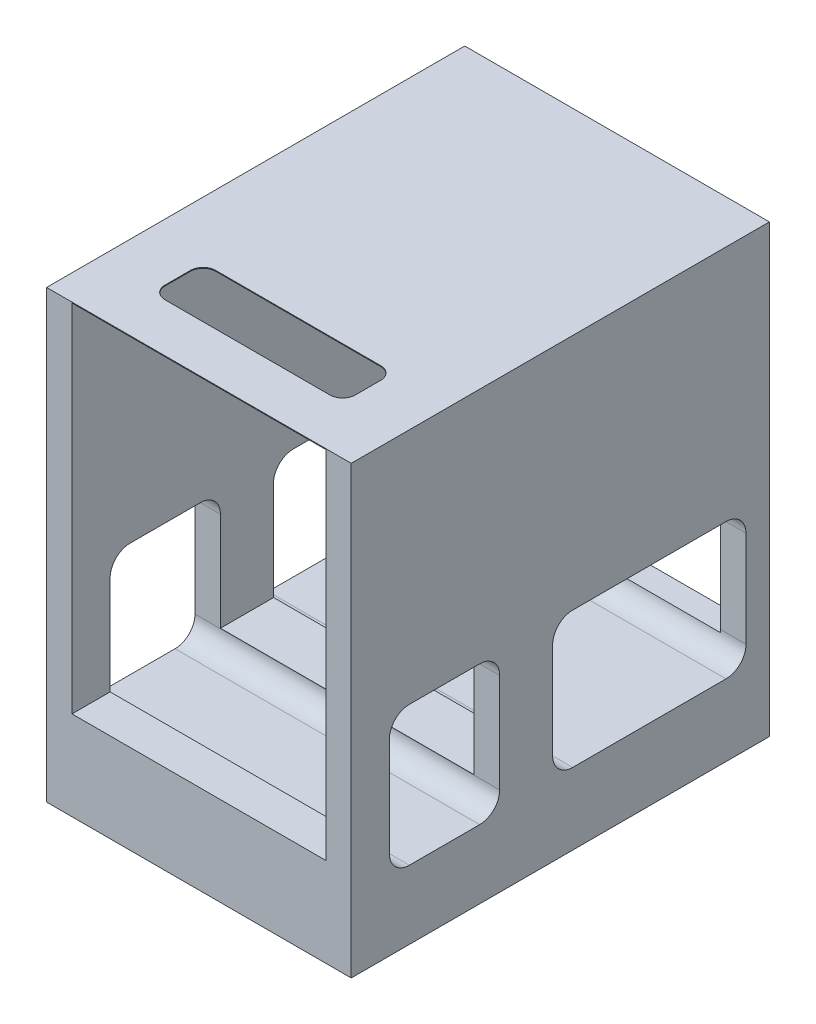
SolidWorks part; units mm, degrees
ref_plane "Front Plane" through (0, 0, 0) normal (0, 0, 1) x (1, 0, 0)
ref_plane "Top Plane" through (0, 0, 0) normal (0, 1, 0) x (1, 0, 0)
ref_plane "Right Plane" through (0, 0, 0) normal (1, 0, 0) x (0, 0, -1)
sketch "Sketch1" plane through (0, 0, 0) normal (0, 1, 0) x (1, 0, 0)
  line L0 (0, 107.4332) -> (0, -101.5151) construction
  line L1 (76.1125, -101.5151) -> (-76.1125, -101.5151)
  line L2 (76.1125, -101.5151) -> (76.1125, 107.4332)
  line L3 (76.1125, 107.4332) -> (-76.1125, 107.4332)
  line L4 (-76.1125, -101.5151) -> (-76.1125, 107.4332)
  line L5 (-76.1125, -597.4296) -> (-76.1125, 267.5849) construction
extrude "Boss-Extrude1" add sketch "Sketch1" along normal up to surface (222.72 mm away)
sketch "Sketch5" plane through (0, 0, 101.5151) normal (0, 0, 1) x (1, 0, 0)
  line L4 (76.1125, 222.72) -> (-76.1125, 222.72)
  line L5 (-76.1125, 222.72) -> (-76.1125, 0)
  line L6 (-76.1125, 0) -> (76.1125, 0)
  line L7 (76.1125, 0) -> (76.1125, 222.72)
  line L8 (65.8631, 222.72) -> (-65.8631, 222.72)
  line L9 (-65.8631, 222.72) -> (-65.8631, 0)
  line L10 (-65.8631, 0) -> (65.8631, 0)
  line L11 (65.8631, 0) -> (65.8631, 222.72)
  point P8 (0, 222.72)
  dimension "D1" = 0
extrude "Boss-Extrude2" [suppressed] add sketch "Sketch5" against normal up to vertex up to point (-76.1125, 0, -107.4332)
sketch "Sketch2" plane through (0, 0, 0) normal (1, 0, 0) x (0, 0, -1)
  line L1 (158.6159, 359.32) -> (-12.7, 359.32)
  line L2 (158.6159, 359.32) -> (158.6159, 232.32)
  line L3 (158.6159, 232.32) -> (-12.7, 232.32)
  line L4 (-12.7, 359.32) -> (-12.7, 232.32)
  line L5 (-108.9263, 232.32) -> (-218.9263, 232.32) construction
  dimension "D2" = 12.7
  dimension "D3" = 171.3159
  dimension "D4" = 127
extrude "Cut-Extrude1" cut sketch "Sketch2" against normal through all both and the other way through all rebuild error yes
sketch "Sketch6" plane through (-76.1125, 0, 0) normal (-1, 0, 0) x (0, 0, 1)
  line L0 (-107.4332, 6.35) -> (12.7, 6.35)
  line L8 (-107.4332, 222.72) -> (-107.4332, 0)
  line L9 (-107.4332, 0) -> (101.5151, 0)
  line L10 (101.5151, 0) -> (101.5151, 222.72)
  line L11 (101.5151, 222.72) -> (-107.4332, 222.72)
  line L14 (-107.4332, 6.35) -> (-107.4332, 0)
  line L15 (-107.4332, 0) -> (101.5151, 0)
  line L16 (101.5151, 0) -> (101.5151, 222.72)
  line L17 (101.5151, 222.72) -> (-107.4332, 222.72)
  dimension "D2" = 6.35
  dimension "D1" = 0
extrude "Boss-Extrude3" add sketch "Sketch6" along normal blind 50.8 rebuild error yes
mirror "Mirror1" about plane through (0, 0, 0) normal (1, 0, 0) rebuild error yes
sketch "Sketch7" plane through (0, 0, -107.4332) normal (0, 0, -1) x (-1, 0, 0)
  line L0 (76.1125, 222.32) -> (-76.1125, 222.32) construction
  line L3 (69.7625, 44.52) -> (-69.7625, 44.52)
  line L6 (69.7625, 0) -> (69.7625, 215.97)
  line L7 (-69.7625, 215.97) -> (-69.7625, 0)
  line L8 (69.7625, 215.97) -> (-69.7625, 215.97)
  line L9 (69.7625, 44.52) -> (69.7625, 222.32)
  line L10 (-69.7625, 222.32) -> (-69.7625, 44.52)
  line L11 (69.7625, 222.32) -> (-69.7625, 222.32)
  dimension "D3" = 177.8
  dimension "D1" = 6.35
extrude "Cut-Extrude4" cut sketch "Sketch7" against normal through all
sketch "Sketch9" plane through (0, 0, 12.7) normal (0, 0, -1) x (-1, 0, 0)
  line L0 (-76.1125, 168.275) -> (-126.9125, 168.275)
  line L7 (76.1125, 222.72) -> (-76.1125, 222.72)
  line L8 (76.1125, 222.72) -> (-76.1125, 222.72)
  line L12 (-76.1125, 222.32) -> (-69.7625, 222.32)
  line L14 (-69.7625, 222.32) -> (69.7625, 222.32)
  line L16 (69.7625, 222.32) -> (76.1125, 222.32)
  line L17 (76.1125, 222.32) -> (76.1125, 222.72)
  line L23 (-76.1125, 222.72) -> (-76.1125, 222.32)
  line L29 (76.1125, 222.72) -> (76.1125, 222.72)
  line L35 (-76.1125, 222.72) -> (-76.1125, 168.275)
  dimension "D1" = 0
extrude "Cut-Extrude6" cut sketch "Sketch9" against normal through all rebuild error yes
sketch "Sketch10" plane through (-69.7625, 0, 0) normal (1, 0, 0) x (0, 0, -1)
  line L6 (107.4332, 44.52) -> (107.4332, 222.32)
  line L9 (107.4332, 222.32) -> (-101.5151, 222.32)
  line L10 (-101.5151, 222.32) -> (-101.5151, 44.52)
  line L11 (-101.5151, 44.52) -> (107.4332, 44.52)
  line L18 (107.4332, 44.52) -> (107.4332, 222.32)
  line L21 (107.4332, 222.32) -> (-101.5151, 222.32)
  line L22 (-101.5151, 222.32) -> (-101.5151, 44.52)
  line L24 (-101.5151, 44.52) -> (107.4332, 44.52)
  dimension "D1" = 0
extrude "Boss-Extrude4" add sketch "Sketch10" along normal blind 6.35
mirror "Mirror2" about plane through (0, 0, 0) normal (1, 0, 0) of "Boss-Extrude4"
chamfer "Chamfer1" distance 19.05 angle 45 rebuild error yes
sketch "Sketch12" plane through (0, 222.32, 0) normal (0, -1, 0) x (1, 0, 0)
  line L0 (63.4125, -107.4332) -> (76.1125, -107.4332) construction
  line L4 (-63.4125, -107.4332) -> (63.4125, -107.4332)
  line L5 (63.4125, -107.4332) -> (63.4125, 101.5151)
  line L6 (63.4125, 101.5151) -> (-63.4125, 101.5151)
  line L7 (-63.4125, 101.5151) -> (-63.4125, -107.4332)
  line L8 (-63.4125, -107.4332) -> (63.4125, -107.4332)
  line L9 (63.4125, -107.4332) -> (63.4125, 101.5151)
  line L10 (63.4125, 101.5151) -> (-63.4125, 101.5151)
  line L11 (-63.4125, 101.5151) -> (-63.4125, -107.4332)
  line L13 (-63.4125, -107.4332) -> (63.4125, -107.4332)
  dimension "D1" = 0
extrude "Boss-Extrude5" add sketch "Sketch12" along normal blind 12.7 rebuild error yes
sketch "Sketch13" plane through (0, 222.72, 0) normal (0, 1, 0) x (1, 0, 0)
  line L0 (0, -51.8774) -> (0, -77.2774) construction
  line L1 (41.2049, -51.8774) -> (-41.2049, -51.8774)
  line L2 (47.5549, -58.2274) -> (47.5549, -70.9274)
  line L3 (41.2049, -77.2774) -> (-41.2049, -77.2774)
  line L4 (-47.5549, -58.2274) -> (-47.5549, -70.9274)
  arc A0 (-41.2049, -51.8774) -> (-47.5549, -58.2274) centre (-41.2049, -58.2274) ccw
  arc A1 (-41.2049, -77.2774) -> (-47.5549, -70.9274) centre (-41.2049, -70.9274) cw
  arc A2 (47.5549, -70.9274) -> (41.2049, -77.2774) centre (41.2049, -70.9274) cw
  arc A3 (41.2049, -51.8774) -> (47.5549, -58.2274) centre (41.2049, -58.2274) cw
  point P9 (-47.5549, -51.8774)
  point P12 (-47.5549, -77.2774)
  dimension "D2" = 6.35
  dimension "D1" = 25.4
extrude "Cut-Extrude8" cut sketch "Sketch13" against normal blind 19.05
fillet "Fillet1" radius 10 rebuild error yes
sketch "Sketch11" plane through (-76.1125, 0, 0) normal (-1, 0, 0) x (0, 0, 1)
  line L0 (-85.7351, 35.8083) -> (-9.1217, 35.8083)
  line L1 (0.8783, 45.8083) -> (0.8783, 93.8742)
  line L2 (-9.1217, 103.8742) -> (-85.7351, 103.8742)
  line L3 (-95.7351, 93.8742) -> (-95.7351, 45.8083)
  line L8 (-338.2977, -825.1709) -> (-307.5827, -825.1709)
  line L9 (-297.5827, -815.1709) -> (-297.5827, -746.7459)
  line L10 (-307.5827, -736.7459) -> (-338.2977, -736.7459)
  line L11 (-348.2977, -746.7459) -> (-348.2977, -815.1709)
  line L12 (37.3544, 34.2868) -> (72.4651, 34.2868)
  line L13 (82.4651, 44.2868) -> (82.4651, 93.8742)
  line L14 (72.4651, 103.8742) -> (37.3544, 103.8742)
  line L15 (27.3544, 93.8742) -> (27.3544, 44.2868)
  arc A0 (72.4651, 34.2868) -> (82.4651, 44.2868) centre (72.4651, 44.2868) ccw
  arc A1 (82.4651, 93.8742) -> (72.4651, 103.8742) centre (72.4651, 93.8742) ccw
  arc A2 (37.3544, 103.8742) -> (27.3544, 93.8742) centre (37.3544, 93.8742) ccw
  arc A3 (37.3544, 34.2868) -> (27.3544, 44.2868) centre (37.3544, 44.2868) cw
  arc A10 (-307.5827, -825.1709) -> (-297.5827, -815.1709) centre (-307.5827, -815.1709) ccw
  arc A11 (-297.5827, -746.7459) -> (-307.5827, -736.7459) centre (-307.5827, -746.7459) ccw
  arc A12 (-338.2977, -736.7459) -> (-348.2977, -746.7459) centre (-338.2977, -746.7459) ccw
  arc A13 (-338.2977, -825.1709) -> (-348.2977, -815.1709) centre (-338.2977, -815.1709) cw
  arc A14 (-9.1217, 35.8083) -> (0.8783, 45.8083) centre (-9.1217, 45.8083) ccw
  arc A15 (0.8783, 93.8742) -> (-9.1217, 103.8742) centre (-9.1217, 93.8742) ccw
  arc A16 (-85.7351, 103.8742) -> (-95.7351, 93.8742) centre (-85.7351, 93.8742) ccw
  arc A17 (-85.7351, 35.8083) -> (-95.7351, 45.8083) centre (-85.7351, 45.8083) cw
  dimension "D2" = 10
  dimension "D3" = 10
  dimension "D1" = 10
extrude "Cut-Extrude7" cut sketch "Sketch11" against normal through all
